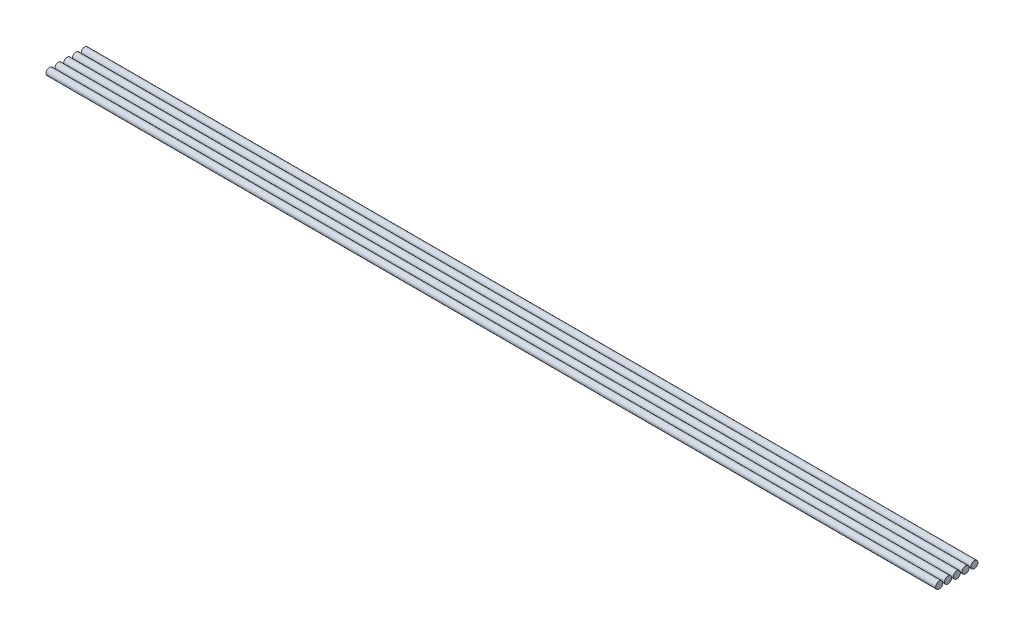
SolidWorks part; units mm, degrees
ref_plane "Front Plane" through (0, 0, 0) normal (0, 0, 1) x (1, 0, 0)
ref_plane "Top Plane" through (0, 0, 0) normal (0, 1, 0) x (1, 0, 0)
ref_plane "Right Plane" through (0, 0, 0) normal (1, 0, 0) x (0, 0, -1)
sketch "Sketch3" plane through (0, 0, 0) normal (0, 1, 0) x (1, 0, 0)
  line L0 (0, 2) -> (101, 2)
  line L1 (0, 1) -> (101, 1)
  line L2 (0, 0) -> (101, 0)
  line L3 (0, -1) -> (101, -1)
  line L4 (0, -2) -> (101, -2)
  line L5 (0, 2) -> (0, -2) construction
  line L6 (101, 2) -> (101, -2) construction
  dimension "D1" = 1
  dimension "D2" = 1
  dimension "D3" = 1
  dimension "D4" = 1
  dimension "D5" = 101
sketch "Sketch21" plane through (0, 0, 0) normal (1, 0, 0) x (0, 0, -1)
  line L0 (2, 0) -> (-2, 0) construction
  circle A0 centre (2, 0) radius 0.4
  circle A1 centre (1, 0) radius 0.4
  circle A2 centre (0, 0) radius 0.4
  circle A3 centre (-1, 0) radius 0.4
  circle A4 centre (-2, 0) radius 0.4
  dimension "D1" = 0.8
sweep "Sweep2" add profiles "Sketch21" path "Sketch3"
